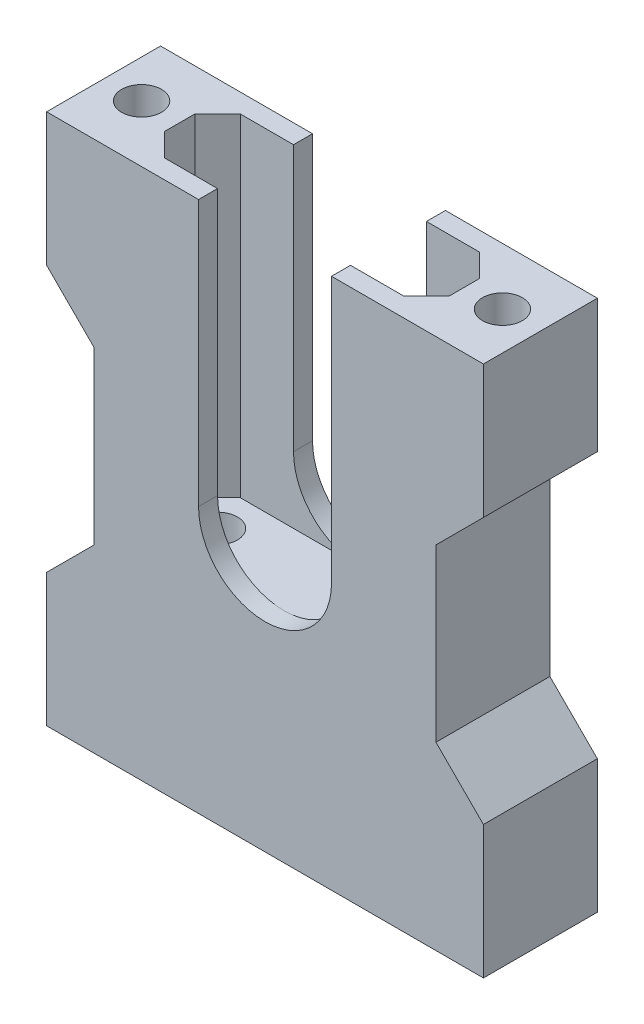
SolidWorks part; units mm, degrees
other "Uwaga1"
sketch "Szkic6" plane through (28, 56, 16) normal (0.3058, 0.389, 0.869) x (0.9408, -0.2636, -0.2131)
sketch "Szkic7" plane through (27, 56, 12) normal (0.3058, 0.389, 0.869) x (0.9408, -0.2636, -0.2131)
sketch "Szkic8" plane through (23, 56, 12) normal (0.3058, 0.389, 0.869) x (0.9408, -0.2636, -0.2131)
sketch "Szkic9" plane through (23, 56, 12) normal (0.3058, 0.389, 0.869) x (0.9408, -0.2636, -0.2131)
material "ABS"
ref_plane "Płaszczyzna przednia" through (0, 0, 0) normal (0, 0, 1) x (1, 0, 0)
ref_plane "Płaszczyzna górna" through (0, 0, 0) normal (0, 1, 0) x (1, 0, 0)
ref_plane "Płaszczyzna prawa" through (0, 0, 0) normal (1, 0, 0) x (0, 0, -1)
sketch "Szkic1" plane through (0, 0, 0) normal (0, 0, 1) x (1, 0, 0)
  line L0 (-23, 0) -> (23, 0)
  line L1 (23, 0) -> (23, 14)
  line L2 (23, 14) -> (18, 19)
  line L3 (18, 19) -> (18, 37)
  line L4 (18, 37) -> (23, 42)
  line L5 (23, 42) -> (23, 56)
  line L7 (-23, 56) -> (-23, 42)
  line L8 (-23, 42) -> (-18, 37)
  line L9 (-18, 37) -> (-18, 19)
  line L10 (-18, 19) -> (-23, 14)
  line L11 (-23, 14) -> (-23, 0)
  line L12 (23, 56) -> (7, 56)
  line L14 (-23, 56) -> (-7, 56)
  line L16 (7, 28) -> (7, 56)
  line L17 (-18, 28) -> (18, 28) construction
  line L18 (-7, 28) -> (-7, 56)
  arc A0 (-7, 28) -> (7, 28) centre (0, 28) ccw
  point P4 (0, 0)
  dimension "D2" = 5
  dimension "D3" = 5
  dimension "D4" = 5
  dimension "D5" = 5
  dimension "D6" = 135
  dimension "D7" = 56
  dimension "D8" = 180
  dimension "D9" = 14
  dimension "D10" = 14
  dimension "D11" = 14
  dimension "D12" = 14
  dimension "D13" = 14
  dimension "D14" = 46
  dimension "D15" = 16
  dimension "D16" = 16
  dimension "D17" = 56
extrude "Dodanie-wyciągnięcie1" add sketch "Szkic1" along normal blind 12
ref_plane "Płaszczyzna1" through (0, 56, 0) normal (0, 1, 0) x (1, 0, 0)
sketch "Szkic2" plane through (0, 56, 0) normal (0, 1, 0) x (1, 0, 0)
  line L0 (0, 0) -> (0, -6) construction
  line L1 (0, -6) -> (-19, -6) construction
  line L2 (0, -6) -> (19, -6) construction
  circle A0 centre (-19, -6) radius 2.1
  circle A1 centre (19, -6) radius 2.1
  dimension "D3" = 4.2
  dimension "D5" = 4.2
  dimension "D1" = 6
  dimension "D2" = 19
  dimension "D4" = 19
extrude "Wytnij-wyciągnięcie1" cut sketch "Szkic2" against normal blind 10
ref_plane "Płaszczyzna2" through (0, 28, 0) normal (0, -1, 0) x (-1, 0, 0)
mirror "Lustro1" about plane through (0, 28, 0) normal (0, -1, 0) of "Wytnij-wyciągnięcie1"
sketch "Szkic3" plane through (0, 56, 0) normal (0, -1, 0) x (-1, 0, 0)
  line L0 (0, 0) -> (0, -6) construction
  line L1 (0, -6) -> (15, -6) construction
  line L2 (15, -10) -> (15, -2) construction
  line L6 (15, -2) -> (12.6, -2) construction
  line L7 (15, -2) -> (15, -4.4) construction
  line L8 (12.6, -2) -> (-12.6, -2)
  line L9 (15, -4.4) -> (12.6, -2)
  line L10 (15, -4.4) -> (15, -7.6)
  line L11 (-15, -4.4) -> (-15, -7.6)
  line L12 (-15, -4.4) -> (-12.6, -2)
  line L13 (-15, -7.6) -> (-12.6, -10)
  line L14 (12.6, -10) -> (-12.6, -10)
  line L15 (15, -7.6) -> (12.6, -10)
  point P7 (15, -6)
  point P13 (0, -2)
  point P14 (-15, -6)
  dimension "D1" = 6
  dimension "D2" = 15
  dimension "D3" = 8
  dimension "D4" = 2.4
  dimension "D5" = 2.4
extrude "Wytnij-wyciągnięcie2" cut sketch "Szkic3" along normal blind 35
sketch "Szkic4" plane through (0, 21, 0) normal (0, 1, 0) x (1, 0, 0)
  line L0 (0, 0) -> (0, -6) construction
  line L1 (-11, -6) -> (11, -6) construction
  circle A0 centre (11, -6) radius 2.1
  circle A1 centre (-11, -6) radius 2.1
  dimension "D3" = 4.2
  dimension "D1" = 6
  dimension "D2" = 11
extrude "Wytnij-wyciągnięcie3" cut sketch "Szkic4" against normal up to next
sketch "Szkic5" plane through (0, 0, 0) normal (0, -1, 0) x (1, 0, 0)
  line L0 (0, -6.6) -> (0, 6.6) construction
  line L1 (11, 1.7276) -> (14.7, 3.8638)
  line L2 (14.7, 3.8638) -> (14.7, 8.1362)
  line L3 (14.7, 8.1362) -> (11, 10.2724)
  line L4 (11, 10.2724) -> (7.3, 8.1362)
  line L5 (7.3, 8.1362) -> (7.3, 3.8638)
  line L6 (7.3, 3.8638) -> (11, 1.7276)
  line L7 (-7.3, 3.8638) -> (-11, 1.7276)
  line L8 (-7.3, 8.1362) -> (-7.3, 3.8638)
  line L9 (-11, 10.2724) -> (-7.3, 8.1362)
  line L10 (-14.7, 8.1362) -> (-11, 10.2724)
  line L11 (-14.7, 3.8638) -> (-14.7, 8.1362)
  line L12 (-11, 1.7276) -> (-14.7, 3.8638)
  circle A0 centre (11, 6) radius 3.7 construction
  circle A1 centre (-11, 6) radius 3.7 construction
  dimension "D1" = 7.4
extrude "Wytnij-wyciągnięcie4" cut sketch "Szkic5" against normal blind 6
equation "\"hight\"=56"
equation "\"D10@Szkic1\"=\"InsertHight\""
equation "\"InsertHight\"=14"
equation "\"D9@Szkic1\"=\"InsertHight\""
equation "\"D11@Szkic1\"=\"InsertHight\""
equation "\"D12@Szkic1\"=\"InsertHight\""
equation "\"FazeX\"= 5"
equation "\"D5@Szkic1\"=\"FazeX\""
equation "\"D4@Szkic1\"=\"FazeX\""
equation "\"D2@Szkic1\"=\"FazeX\""
equation "\"D3@Szkic1\"=\"FazeX\""
equation "\"width\"= 46"
equation "\"D15@Szkic1\"=\"TopWidth\""
equation "\"TopWidth\"= 16"
equation "\"D16@Szkic1\"=\"TopWidth\""
equation "\"D7@Szkic1\"=\"hight\""
equation "\"D17@Szkic1\"=\"hight\""
equation "\"depth\"= 12"
equation "\"D1@Szkic2\"=\"depth\"/2"
equation "\"D1@Dodanie-wyciągnięcie1\"=\"depth\""
equation "\"D14@Szkic1\"=\"width\""
equation "\"ToInsertX\"= ( \"width\" - \"TopWidth\" - \"TopWidth\" ) / 2 + ( \"TopWidth\" / 2 ) + \"FazeX\" * 0.8"
equation "\"InsertDiameter\"= 4.2"
equation "\"D3@Szkic2\"=\"InsertDiameter\""
equation "\"D2@Szkic2\"=\"ToInsertX\""
equation "\"D4@Szkic2\"=\"ToInsertX\""
equation "\"D5@Szkic2\"=\"InsertDiameter\""
equation "\"InsertDepth\"=10"
equation "\"D1@Wytnij-wyciągnięcie1\"=\"InsertDepth\""
equation "\"Diameter\"= \"width\" - \"TopWidth\" - \"TopWidth\""
equation "\"D1@Szkic3\"=\"depth\"/2"
equation "\"RailX\"= 8"
equation "\"D2@Szkic3\"=\"Diameter\"/2+\"RailX\""
equation "\"RailZ\"= 8"
equation "\"D3@Szkic3\"=\"RailZ\""
equation "\"D1@Wytnij-wyciągnięcie2\"=\"hight\"/2+\"Diameter\"/2"
equation "\"D4@Szkic3\" = \"RailZ\" * 0.3"
equation "\"D5@Szkic3\" = \"RailZ\" * 0.3"
equation "\"D1@Szkic4\"=\"depth\"/2"
equation "\"D2@Szkic4\"=\"Diameter\"/2+\"RailX\"/2"
